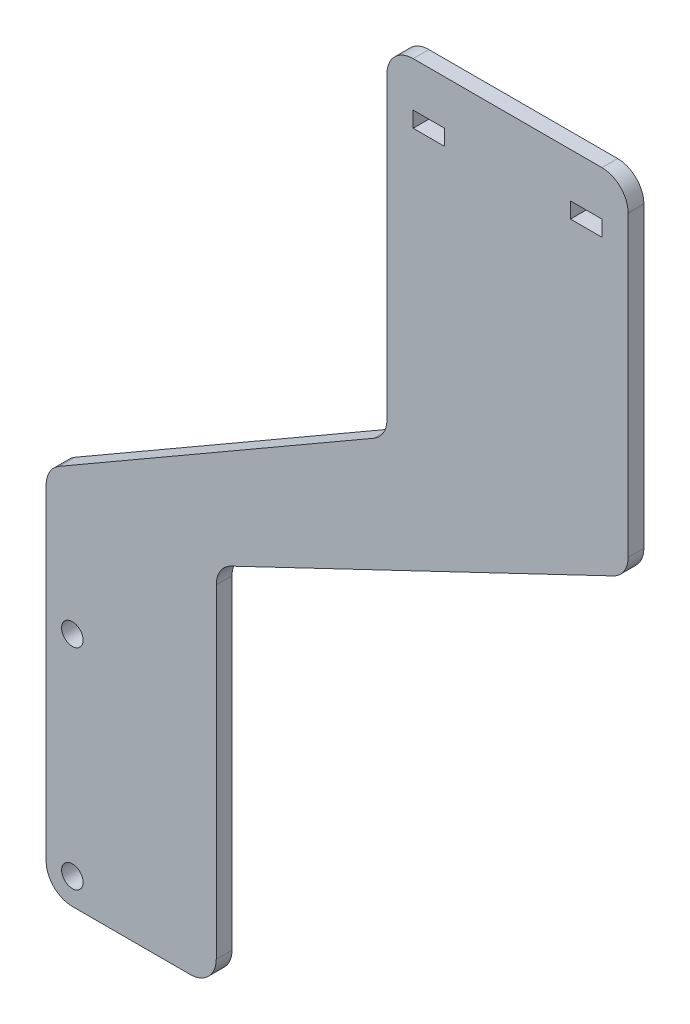
SolidWorks part; units mm, degrees
ref_plane "Front Plane" through (0, 0, 0) normal (0, 0, 1) x (1, 0, 0)
ref_plane "Top Plane" through (0, 0, 0) normal (0, 1, 0) x (1, 0, 0)
ref_plane "Right Plane" through (0, 0, 0) normal (1, 0, 0) x (0, 0, -1)
sketch "Sketch1" plane through (0, 0, 0) normal (0, 0, 1) x (1, 0, 0)
  line L0 (-78.6038, -5.5278) -> (-111.0529, -5.5278)
  line L1 (-111.0529, -5.5278) -> (-111.0529, 64.4722)
  line L3 (-46.0529, 102) -> (-46.0529, 167)
  line L4 (-46.0529, 167) -> (-0.0529, 167)
  line L5 (-0.0529, 167) -> (-0.0529, 102)
  line L6 (-106.0529, 39.4722) -> (-106.0529, -18.7631) construction
  line L7 (-23.0529, 167) -> (-23.0529, 157) construction
  line L8 (-23.0529, 157) -> (-1.1451, 157) construction
  line L9 (-35.0529, 158.5) -> (-35.0529, 155.5)
  line L10 (-11.0529, 158.5) -> (-5.0529, 158.5)
  line L11 (-11.0529, 158.5) -> (-11.0529, 155.5)
  line L12 (-11.0529, 155.5) -> (-5.0529, 155.5)
  line L13 (-5.0529, 158.5) -> (-5.0529, 155.5)
  line L14 (-11.0529, 158.5) -> (-5.0529, 155.5) construction
  line L15 (-11.0529, 155.5) -> (-5.0529, 158.5) construction
  line L16 (-35.0529, 155.5) -> (-41.0529, 155.5)
  line L17 (-41.0529, 158.5) -> (-41.0529, 155.5)
  line L18 (-35.0529, 158.5) -> (-41.0529, 158.5)
  line L19 (-46.0529, 102) -> (-111.0529, 64.4722)
  line L21 (-0.0529, 102) -> (-46.0529, 102) construction
  line L22 (-78.6038, 45.0439) -> (-78.6038, -5.5278)
  line L23 (-111.0529, 64.4722) -> (-78.6038, 64.4722) construction
  line L24 (-78.6038, 45.0439) -> (-78.6038, 64.4722)
  line L25 (-78.6038, 64.4722) -> (-0.0529, 102)
  circle A0 centre (-106.0529, 39.4722) radius 2.05
  circle A1 centre (-106.0529, -0.5278) radius 2.05
  point P2 (-0.1759, 99.1295)
  point P15 (-8.0529, 157)
  dimension "D1" = 4.1
  dimension "D3" = 5
  dimension "D7" = 40
  dimension "D2" = 5
  dimension "D4" = 60
  dimension "D5" = 46
  dimension "D6" = 120
  dimension "D8" = 70
  dimension "D9" = 6
  dimension "D10" = 3
  dimension "D11" = 15
  dimension "D12" = 10
  dimension "D13" = 65
extrude "Boss-Extrude1" add sketch "Sketch1" along normal blind 3
fillet "Fillet1" radius 5 8 edges at (-46.0529, 167, 1.5) (-0.0529, 167, 1.5) (-111.0529, -5.5278, 1.5) (-46.0529, 102, 1.5) (-111.0529, 64.4722, 1.5) (-78.6038, -5.5278, 1.5) (-78.6038, 64.4722, 1.5) (-0.0529, 102, 1.5)
